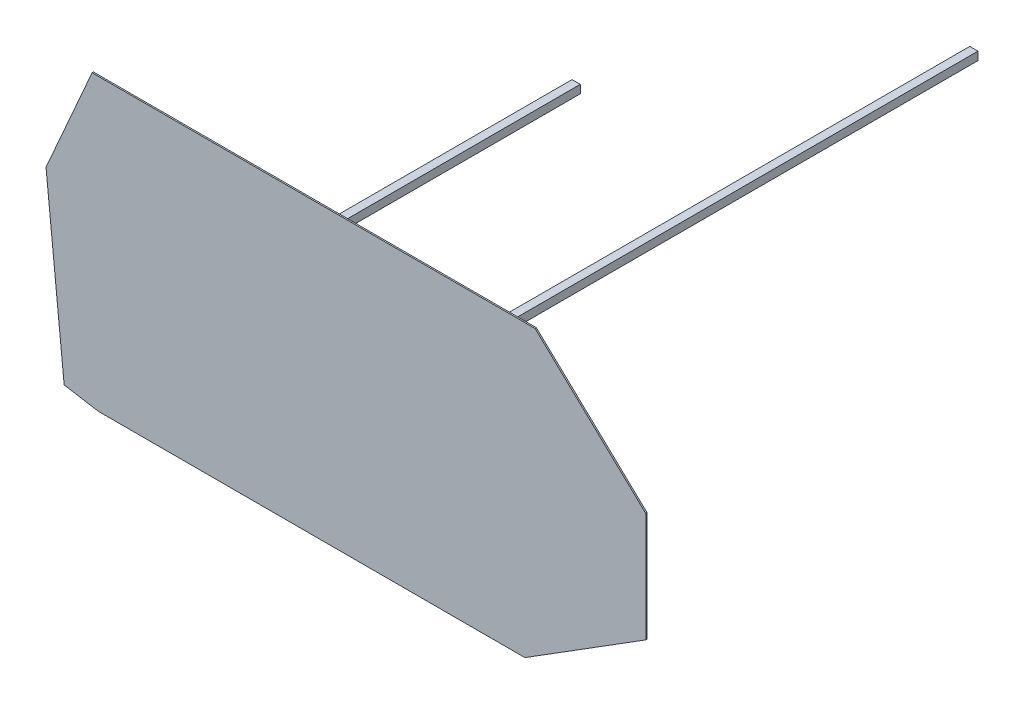
SolidWorks part; units mm, degrees
ref_plane "Front" through (0, 0, 0) normal (0, 0, 1) x (1, 0, 0)
ref_plane "Top" through (0, 0, 0) normal (0, 1, 0) x (1, 0, 0)
ref_plane "Right" through (0, 0, 0) normal (1, 0, 0) x (0, 0, -1)
sketch "Esquisse1" plane through (0, 0, 0) normal (0, 0, 1) x (1, 0, 0)
  line L1 (0, 0) -> (50, 0)
  line L2 (0, 0) -> (0, 50)
  line L3 (0, 50) -> (50, 50)
  line L4 (50, 0) -> (50, 50)
  dimension "D1" = 50
  dimension "D2" = 50
extrude "Boss.-Extru.1" add sketch "Esquisse1" along normal blind 5
sketch "Esquisse2" plane through (0, 0, 5) normal (0, 0, 1) x (1, 0, 0)
  line L0 (-5.6535, 9.3332) -> (57.2852, 53.4636)
  line L1 (57.2852, 53.4636) -> (231.6916, 53.4636)
  line L2 (231.6916, 53.4636) -> (285.9358, -3.0527)
  line L3 (285.9358, -3.0527) -> (284, -82.5096)
  line L4 (284, -82.5096) -> (207.7062, -129.7611)
  line L5 (207.7062, -129.7611) -> (50.4315, -129.7611)
  line L6 (50.4315, -129.7611) -> (-5.6535, -85.3866)
  line L7 (-5.6535, -85.3866) -> (-5.6535, 9.3332)
  line L8 (261, -129.7611) -> (23, -129.7611) construction
  line L9 (284, 24.7389) -> (284, -104.2611) construction
extrude "Boss.-Extru.2" add sketch "Esquisse2" against normal up to vertex (5 mm away) up to point (0, 50, 0)
sketch "Esquisse3" plane through (0, 0, 0) normal (0, 0, -1) x (-1, 0, 0)
  line L0 (0, -121.7217) -> (6, -121.7217)
  line L1 (6, -121.7217) -> (6, -115.7217)
  line L2 (6, -115.7217) -> (0, -115.7217)
  line L4 (0, -115.7217) -> (0, -121.7217)
  line L6 (-284, 44.2389) -> (-290, 44.2389)
  line L7 (-284, 44.2389) -> (-284, 50.2389)
  line L8 (-284, 50.2389) -> (-290, 50.2389)
  line L9 (-290, 44.2389) -> (-290, 50.2389)
  dimension "D1" = 6
  dimension "D2" = 6
  dimension "D3" = 6
  dimension "D4" = 6
extrude "Boss.-Extru.3" add sketch "Esquisse3" along normal blind 350
sketch "Esquisse4" plane through (0, 0, 5) normal (0, 0, 1) x (1, 0, 0)
  line L0 (0, 69.5906) -> (322.9861, 69.5906)
  line L1 (322.9861, 69.5906) -> (403.7416, -6.8693)
  line L2 (403.7416, -6.8693) -> (403.7416, -86.7162)
  line L3 (403.7416, -86.7162) -> (315.5911, -141.9628)
  line L4 (315.5911, -141.9628) -> (4.7577, -141.9628)
  line L5 (4.7577, -141.9628) -> (-20.3705, -137.7747)
  line L6 (-20.3705, -137.7747) -> (-33.6198, -6.8693)
  line L7 (-33.6198, -6.8693) -> (0, 69.5906)
  point P2 (403.7416, -6.8693)
  point P9 (303.7949, 87.7611)
  point P10 (-33.6198, -6.8693)
  point P11 (0, 69.5906)
  point P12 (-20.3705, -137.7747)
  point P13 (4.7577, -141.9628)
extrude "Boss.-Extru.4" add sketch "Esquisse4" along normal blind 1
